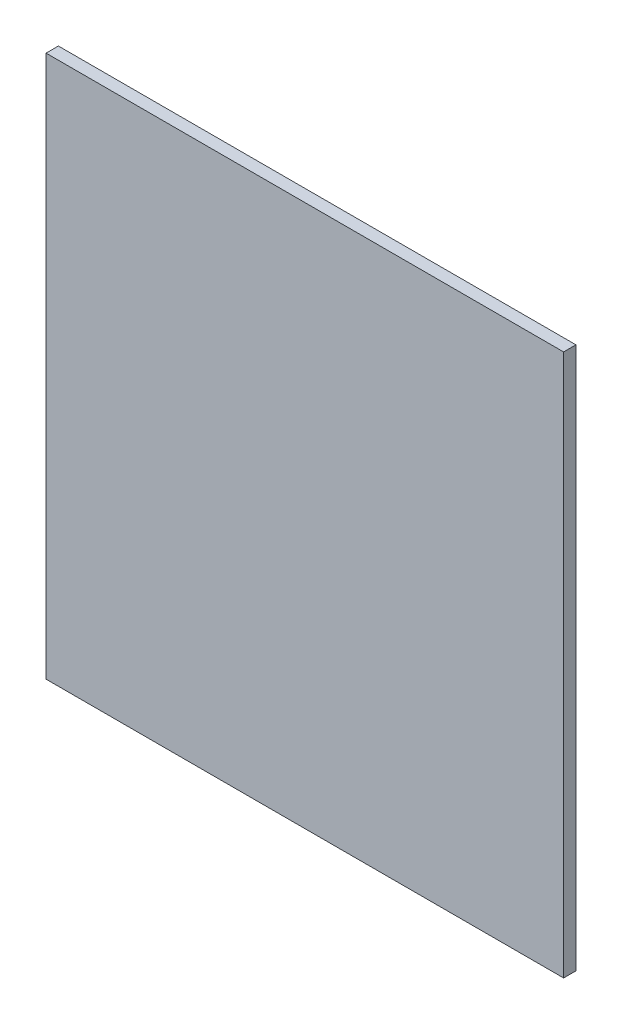
SolidWorks part; units mm, degrees
ref_plane "Front Plane" through (0, 0, 0) normal (0, 0, 1) x (1, 0, 0)
ref_plane "Top Plane" through (0, 0, 0) normal (0, 1, 0) x (1, 0, 0)
ref_plane "Right Plane" through (0, 0, 0) normal (1, 0, 0) x (0, 0, -1)
sketch "Sketch1" plane through (0, 0, 0) normal (0, 0, 1) x (1, 0, 0)
  line L1 (-69.8547, 63.883) -> (14.1453, 63.883)
  line L2 (-69.8547, 63.883) -> (-69.8547, -24.117)
  line L3 (-69.8547, -24.117) -> (14.1453, -24.117)
  line L4 (14.1453, 63.883) -> (14.1453, -24.117)
  dimension "D1" = 84
  dimension "D2" = 88
extrude "Boss-Extrude1" add sketch "Sketch1" along normal blind 2
